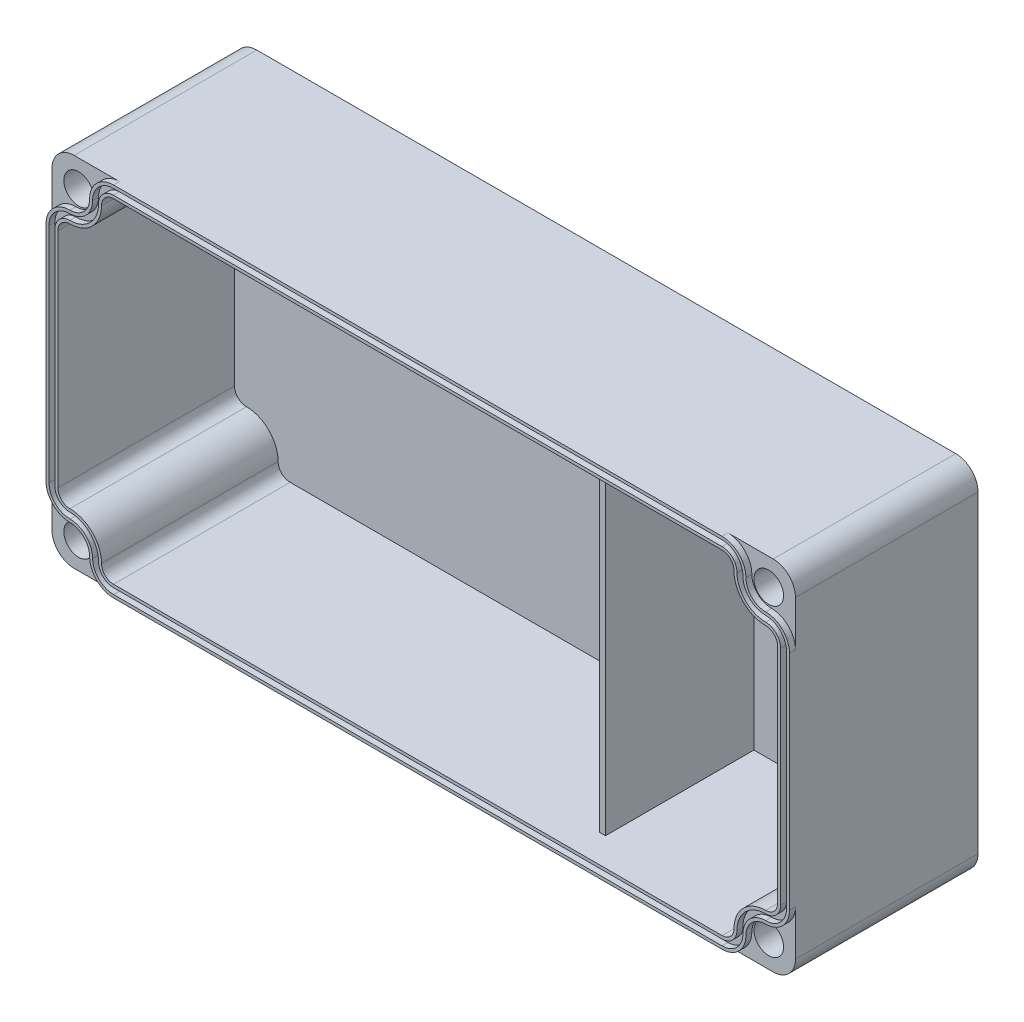
SolidWorks part; units mm, degrees
ref_plane "Plan de face" through (0, 0, 0) normal (0, 0, 1) x (1, 0, 0)
ref_plane "Plan de dessus" through (0, 0, 0) normal (0, 1, 0) x (1, 0, 0)
ref_plane "Plan de droite" through (0, 0, 0) normal (1, 0, 0) x (0, 0, -1)
sketch "Esquisse1" plane through (0, 0, 0) normal (0, 0, 1) x (1, 0, 0)
  line L1 (-48.5, 22.5) -> (48.5, 22.5)
  line L2 (-48.5, 22.5) -> (-48.5, -22.5)
  line L3 (-48.5, -22.5) -> (48.5, -22.5)
  line L4 (48.5, 22.5) -> (48.5, -22.5)
  line L5 (-48.5, 22.5) -> (48.5, -22.5) construction
  line L6 (-48.5, -22.5) -> (48.5, 22.5) construction
  point P0 (0, 0)
  dimension "D1" = 97
  dimension "D2" = 45
extrude "Boss.-Extru.1" add sketch "Esquisse1" along normal blind 23
shell "Coque1" thickness 1.6 removed face at (0, 0, 23) outward yes
ref_plane "Plan1" through (0, 0, 20) normal (0, 0, 1) x (1, 0, 0)
sketch "Esquisse8" plane through (0, 0, 20) normal (0, 0, 1) x (1, 0, 0)
  line L0 (21.5, 16.8946) -> (21.5, -12.3256)
  line L1 (48.5, -22.5) -> (48.5, 22.5) construction
  dimension "D1" = 27
rib "Nervure18" sketch "Esquisse8" sketch "Esquisse8" thickness 0.8 extrusion direction normal to sketch draft on no parameters "D1"=0.8
sketch "Esquisse10" plane through (0, 0, 0) normal (0, 0, 1) x (1, 0, 0)
  line L0 (-48.5, 22.5) -> (-48.5, 15)
  line L1 (-48.5, 22.5) -> (-48.5, -22.5) construction
  line L2 (20.7, 22.5) -> (-48.5, 22.5) construction
  line L3 (-41, 22.5) -> (-48.5, 22.5)
  line L4 (-46.88, 15) -> (-48.5, 15) construction
  line L5 (-46.88, 15) -> (-46.88, 16.62) construction
  line L6 (-41, 20.88) -> (-42.62, 20.88) construction
  line L7 (-41, 20.88) -> (-41, 22.5) construction
  arc A1 (-48.5, 15) -> (-46.88, 16.62) centre (-46.88, 15) cw
  arc A2 (-46.88, 16.62) -> (-42.62, 20.88) centre (-46.88, 20.88) ccw
  arc A3 (-42.62, 20.88) -> (-41, 22.5) centre (-41, 20.88) cw
  dimension "D1" = 7.5
extrude "Boss.-Extru.2" add sketch "Esquisse10" along normal up to surface (23 mm away) up to face at (0, 0, 23)
mirror "Symétrie1" about plane through (0, 0, 0) normal (1, 0, 0) of "Boss.-Extru.2"
mirror "Symétrie2" about plane through (0, 0, 0) normal (0, 1, 0) of "Boss.-Extru.2"
mirror "Symétrie3" about plane through (0, 0, 0) normal (0, 1, 0) of "Symétrie1"
sketch "Esquisse13" plane through (0, 0, 23) normal (0, 0, 1) x (1, 0, 0)
  line L0 (-46.5, 20.5) -> (-46.5, 22.5) construction
  line L1 (50.1, 24.1) -> (-50.1, 24.1) construction
  line L2 (-46.5, 20.5) -> (-48.5, 20.5) construction
  line L4 (-50.1, 24.1) -> (-50.1, -24.1) construction
  circle A0 centre (-46.5, 20.5) radius 2
  dimension "D1" = 4
  dimension "D2" = 1.6
  dimension "D3" = 1.6
extrude "Enlèv. mat.-Extru.1" cut sketch "Esquisse13" against normal blind 5.7
mirror "Symétrie4" about plane through (0, 0, 0) normal (1, 0, 0) of "Enlèv. mat.-Extru.1"
mirror "Symétrie5" about plane through (0, 0, 0) normal (0, 1, 0) of "Symétrie4"
sketch "Esquisse14" plane through (0, 0, 23) normal (0, 0, 1) x (1, 0, 0)
  line L0 (-41, 22.5) -> (41, 22.5)
  line L1 (48.5, 15) -> (48.5, -15)
  line L2 (41, -22.5) -> (-41, -22.5)
  line L3 (-48.5, -15) -> (-48.5, 15)
  line L4 (-49.7, -15) -> (-49.7, 15)
  line L5 (-41, 23.7) -> (41, 23.7)
  line L6 (49.7, 15) -> (49.7, -15)
  line L7 (41, -23.7) -> (-41, -23.7)
  arc A0 (41, 22.5) -> (42.62, 20.88) centre (41, 20.88) cw
  arc A1 (42.62, 20.88) -> (46.88, 16.62) centre (46.88, 20.88) ccw
  arc A2 (46.88, 16.62) -> (48.5, 15) centre (46.88, 15) cw
  arc A3 (48.5, -15) -> (46.88, -16.62) centre (46.88, -15) cw
  arc A4 (46.88, -16.62) -> (42.62, -20.88) centre (46.88, -20.88) ccw
  arc A5 (42.62, -20.88) -> (41, -22.5) centre (41, -20.88) cw
  arc A6 (-41, -22.5) -> (-42.62, -20.88) centre (-41, -20.88) cw
  arc A7 (-42.62, -20.88) -> (-46.88, -16.62) centre (-46.88, -20.88) ccw
  arc A8 (-46.88, -16.62) -> (-48.5, -15) centre (-46.88, -15) cw
  arc A9 (-48.5, 15) -> (-46.88, 16.62) centre (-46.88, 15) cw
  arc A10 (-46.88, 16.62) -> (-42.62, 20.88) centre (-46.88, 20.88) ccw
  arc A11 (-42.62, 20.88) -> (-41, 22.5) centre (-41, 20.88) cw
  arc A12 (-49.7, 15) -> (-46.88, 17.82) centre (-46.88, 15) cw
  arc A13 (-46.88, 17.82) -> (-43.82, 20.88) centre (-46.88, 20.88) ccw
  arc A14 (-43.82, 20.88) -> (-41, 23.7) centre (-41, 20.88) cw
  arc A15 (41, 23.7) -> (43.82, 20.88) centre (41, 20.88) cw
  arc A16 (43.82, 20.88) -> (46.88, 17.82) centre (46.88, 20.88) ccw
  arc A17 (46.88, 17.82) -> (49.7, 15) centre (46.88, 15) cw
  arc A18 (49.7, -15) -> (46.88, -17.82) centre (46.88, -15) cw
  arc A19 (46.88, -17.82) -> (43.82, -20.88) centre (46.88, -20.88) ccw
  arc A20 (43.82, -20.88) -> (41, -23.7) centre (41, -20.88) cw
  arc A21 (-41, -23.7) -> (-43.82, -20.88) centre (-41, -20.88) cw
  arc A22 (-43.82, -20.88) -> (-46.88, -17.82) centre (-46.88, -20.88) ccw
  arc A23 (-46.88, -17.82) -> (-49.7, -15) centre (-46.88, -15) cw
  dimension "D1" = 1.2
extrude "Extru.-Mince1" add sketch "Esquisse14" along normal blind 0.8 thin thin type one direction wall 0.4
fillet "Congé1" radius 3 4 edges at (-50.1, -24.1, 10.7) (50.1, -24.1, 10.7) (50.1, 24.1, 10.7) (-50.1, 24.1, 10.7)
sketch "Esquisse15" plane through (0, 0, 0) normal (0, 0, 1) x (1, 0, 0)
  line L0 (-50.1, -15) -> (-50.1, 21.1)
  line L1 (-47.1, 24.1) -> (47.1, 24.1)
  line L2 (50.1, 21.1) -> (50.1, -21.1)
  line L3 (47.1, -24.1) -> (-47.1, -24.1)
  line L4 (-50.1, -21.1) -> (-50.1, -15)
  arc A0 (-50.1, 21.1) -> (-47.1, 24.1) centre (-47.1, 21.1) cw
  arc A1 (47.1, 24.1) -> (50.1, 21.1) centre (47.1, 21.1) cw
  arc A2 (50.1, -21.1) -> (47.1, -24.1) centre (47.1, -21.1) cw
  arc A3 (-47.1, -24.1) -> (-50.1, -21.1) centre (-47.1, -21.1) cw
sketch "Esquisse16" plane through (0, 0, 0) normal (0, 0, 1) x (1, 0, 0)
  circle A0 centre (-31.1716, 18.1378) radius 1.5
  circle A1 centre (14.1284, 18.1378) radius 1.5
  circle A2 centre (14.1284, -17.7622) radius 1.5
  point P0 (-31.1716, 18.1378)
  dimension "D1" = 3
  dimension "D2" = 3
  dimension "D3" = 3
extrude "Boss.-Extru.3" add sketch "Esquisse16" along normal blind 6
fillet "Congé2" radius 2 3 edges at (15.6284, -17.7622, 0) (15.6284, 18.1378, 0) (-29.6716, 18.1378, 0)
equation "\"buse\"= 0.8"
equation "\"D1@Coque1\"=\"buse\"*2"
equation "\"hauteur\"=10"
equation "\"D1@Nervure1\"=\"hauteur\""
equation "\"D1@Nervure18\"=\"buse\""
equation "\"D2@Esquisse13\"=\"buse\"*2"
equation "\"D3@Esquisse13\"=2*\"buse\""
